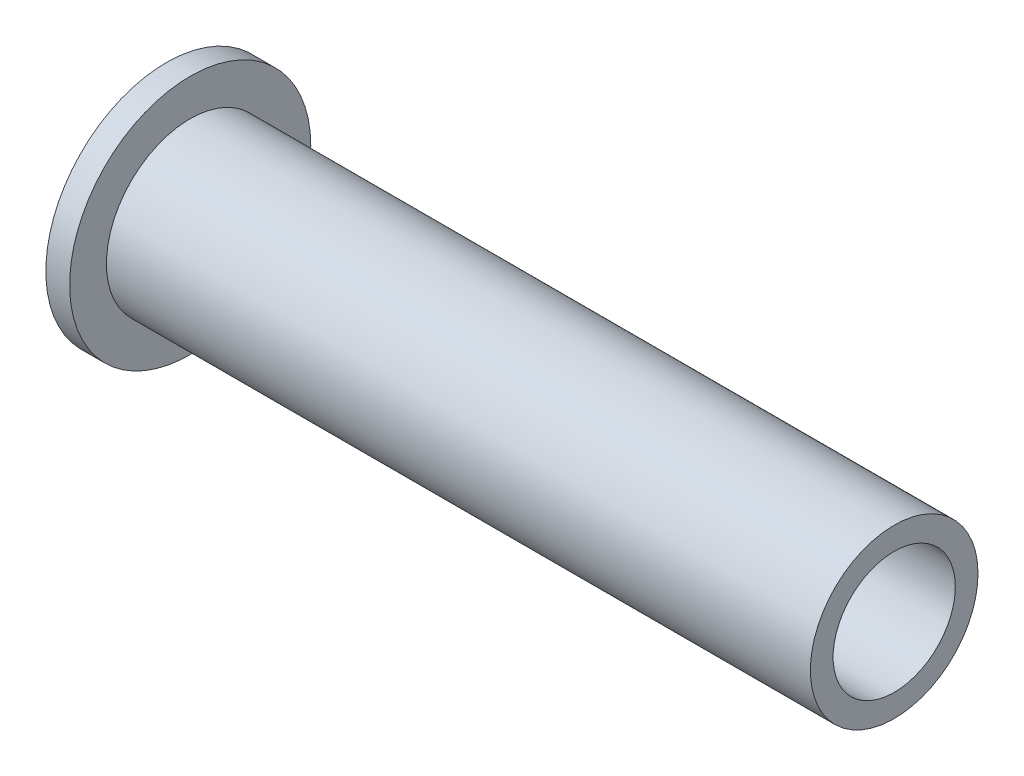
SolidWorks part; units mm, degrees
ref_plane "Front Plane" through (0, 0, 0) normal (0, 0, 1) x (1, 0, 0)
ref_plane "Top Plane" through (0, 0, 0) normal (0, 1, 0) x (1, 0, 0)
ref_plane "Right Plane" through (0, 0, 0) normal (1, 0, 0) x (0, 0, -1)
sketch "Sketch1" plane through (0, 0, 0) normal (0, 0, 1) x (1, 0, 0)
  line L0 (0, 0) -> (17.0942, 0)
  line L1 (17.0942, 0) -> (17.0942, 1.9685)
  line L2 (17.0942, 1.9685) -> (0.5588, 1.9685)
  line L3 (0.5588, 1.9685) -> (0.5588, 2.8321)
  line L4 (0.5588, 2.8321) -> (0, 2.8321)
  line L5 (0, 2.8321) -> (0, 0)
  line L6 (0, 0) -> (-7.6462, 0) construction
  dimension "D1" = 17.0942
  dimension "D2" = 1.9685
  dimension "D3" = 2.8321
  dimension "D4" = 0.5588
revolve "Revolve1" add sketch "Sketch1" angle 360 about L6
sketch "Sketch2" plane through (0, 0, 0) normal (-1, 0, 0) x (0, 0, 1)
  line L0 (0, 0) -> (0, 1.778) construction
  line L1 (0, 0) -> (0, -1.778) construction
  line L2 (0, 0) -> (1.5398, 0.889) construction
  line L4 (0, 0) -> (1.5398, -0.889) construction
  line L6 (-1.5398, 0.889) -> (-1.0479, 0)
  line L7 (-1.0479, 0) -> (-1.5618, -0.8765)
  line L10 (-1.5398, 0.889) -> (-0.524, 0.9075)
  line L11 (-0.524, 0.9075) -> (0, 1.778)
  line L12 (0, 1.778) -> (0.524, 0.9075)
  line L13 (0.524, 0.9075) -> (1.5398, 0.889)
  line L14 (1.5398, 0.889) -> (1.0479, 0)
  line L15 (1.0479, 0) -> (1.5398, -0.889)
  line L16 (1.5398, -0.889) -> (0.524, -0.9075)
  line L17 (0.524, -0.9075) -> (0, -1.778)
  line L18 (0, -1.778) -> (-0.5468, -0.9217)
  line L19 (-0.5468, -0.9217) -> (-1.5618, -0.8765)
  dimension "D1" = 3.556
  dimension "D2" = 60
  dimension "D4" = 60
  dimension "D6" = 1.016
extrude "Cut-Extrude1" cut sketch "Sketch2" against normal blind 0.762
hole_wizard "#6-40 Tapped Hole1" positions "Sketch3" profile "Sketch4" tap size "#6-40" standard "ANSI Inch"
sketch "Sketch3" plane through (17.0942, 0, 0) normal (1, 0, 0) x (0, 0, -1)
  point P0 (0, 0)
sketch "Sketch4" plane through (17.0942, 0, 0) normal (0, 1, 0) x (0, 0, -1)
  line L0 (0, 0) -> (0, 10.5143)
  line L1 (0, 10.5143) -> (1.4351, 9.652)
  line L2 (1.4351, 9.652) -> (1.4351, 0)
  line L5 (1.4351, 0) -> (0, 0)
  line L10 (0, 10.5143) -> (-1.4351, 9.652) construction
  line L11 (0, -6.35) -> (0, 107.95) construction
  dimension "Tap Drill Dia." = 2.8702
  dimension "Tap Drill Depth" = 9.652
  dimension "Drill Angle" = 118
